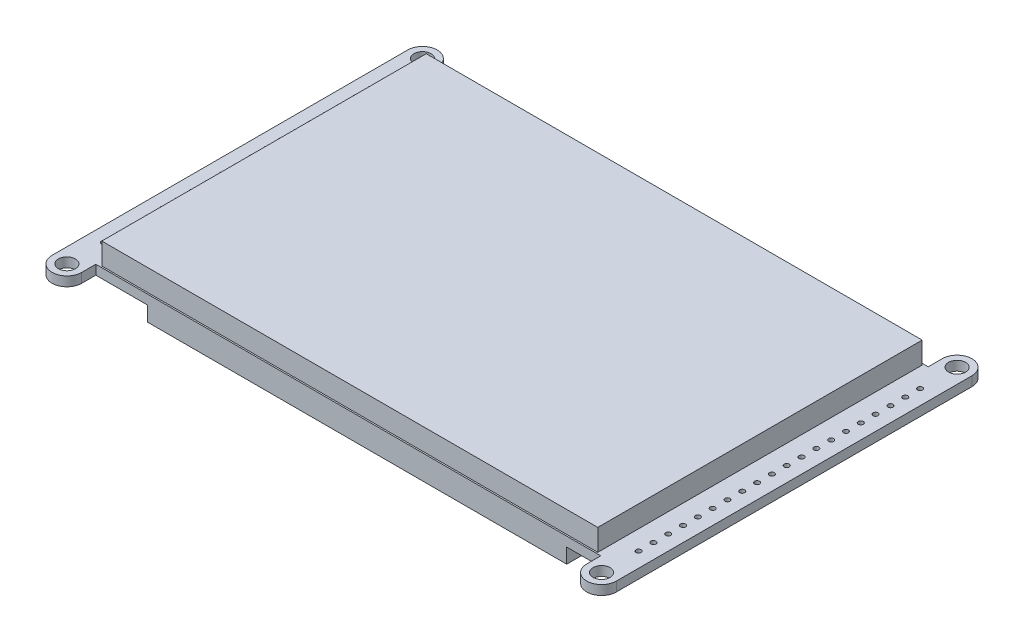
SolidWorks part; units mm, degrees
ref_plane "Front Plane" through (0, 0, 0) normal (0, 0, 1) x (1, 0, 0)
ref_plane "Top Plane" through (0, 0, 0) normal (0, 1, 0) x (1, 0, 0)
ref_plane "Right Plane" through (0, 0, 0) normal (1, 0, 0) x (0, 0, -1)
sketch "Sketch1" plane through (0, 0, 0) normal (0, 1, 0) x (1, 0, 0)
  line L0 (0, -28.067) -> (0, 28.067) construction
  line L1 (43.2943, 28.067) -> (-43.2943, 28.067)
  line L2 (43.2943, -28.067) -> (-43.2943, -28.067)
  line L3 (-43.2943, 28.067) -> (-43.2943, 30.48)
  line L4 (-48.3743, 30.48) -> (-48.3743, -30.48)
  line L5 (-43.2943, -30.48) -> (-43.2943, -28.067)
  line L6 (43.2943, -30.48) -> (43.2943, -28.067)
  line L7 (43.2943, 28.067) -> (43.2943, 30.48)
  line L8 (48.3743, 30.48) -> (48.3743, -30.48)
  line L9 (-45.8343, 24.13) -> (-45.8343, -24.13) construction
  line L10 (45.8343, 24.13) -> (45.8343, -24.13) construction
  line L12 (42.5196, -27.813) -> (-42.5196, -27.813)
  line L13 (42.5196, -27.813) -> (42.5196, 27.813)
  line L14 (42.5196, 27.813) -> (-42.5196, 27.813)
  line L15 (-42.5196, -27.813) -> (-42.5196, 27.813)
  line L16 (42.5196, -27.813) -> (-42.5196, 27.813) construction
  line L17 (42.5196, 27.813) -> (-42.5196, -27.813) construction
  circle A0 centre (-45.8343, 30.48) radius 1.4605
  arc A1 (-43.2943, 30.48) -> (-48.3743, 30.48) centre (-45.8343, 30.48) ccw
  arc A2 (-48.3743, -30.48) -> (-43.2943, -30.48) centre (-45.8343, -30.48) ccw
  circle A3 centre (-45.8343, -30.48) radius 1.4605
  circle A4 centre (45.8343, -30.48) radius 1.4605
  arc A5 (48.3743, -30.48) -> (43.2943, -30.48) centre (45.8343, -30.48) cw
  arc A6 (43.2943, 30.48) -> (48.3743, 30.48) centre (45.8343, 30.48) cw
  circle A7 centre (45.8343, 30.48) radius 1.4605
  circle A8 centre (-45.8343, 24.13) radius 0.4318
  circle A9 centre (-45.8343, 21.59) radius 0.4318
  circle A10 centre (-45.8343, 19.05) radius 0.4318
  circle A11 centre (-45.8343, 16.51) radius 0.4318
  circle A12 centre (-45.8343, 13.97) radius 0.4318
  circle A13 centre (-45.8343, 11.43) radius 0.4318
  circle A14 centre (-45.8343, 8.89) radius 0.4318
  circle A15 centre (-45.8343, 6.35) radius 0.4318
  circle A16 centre (-45.8343, 3.81) radius 0.4318
  circle A17 centre (-45.8343, 1.27) radius 0.4318
  circle A18 centre (-45.8343, -1.27) radius 0.4318
  circle A19 centre (-45.8343, -3.81) radius 0.4318
  circle A20 centre (-45.8343, -6.35) radius 0.4318
  circle A21 centre (-45.8343, -8.89) radius 0.4318
  circle A22 centre (-45.8343, -11.43) radius 0.4318
  circle A23 centre (-45.8343, -13.97) radius 0.4318
  circle A24 centre (-45.8343, -16.51) radius 0.4318
  circle A25 centre (-45.8343, -19.05) radius 0.4318
  circle A26 centre (-45.8343, -21.59) radius 0.4318
  circle A27 centre (-45.8343, -24.13) radius 0.4318
  circle A28 centre (45.8343, -24.13) radius 0.4318
  circle A29 centre (45.8343, -21.59) radius 0.4318
  circle A30 centre (45.8343, -19.05) radius 0.4318
  circle A31 centre (45.8343, -16.51) radius 0.4318
  circle A32 centre (45.8343, -13.97) radius 0.4318
  circle A33 centre (45.8343, -11.43) radius 0.4318
  circle A34 centre (45.8343, -8.89) radius 0.4318
  circle A35 centre (45.8343, -6.35) radius 0.4318
  circle A36 centre (45.8343, -3.81) radius 0.4318
  circle A37 centre (45.8343, -1.27) radius 0.4318
  circle A38 centre (45.8343, 1.27) radius 0.4318
  circle A39 centre (45.8343, 3.81) radius 0.4318
  circle A40 centre (45.8343, 6.35) radius 0.4318
  circle A41 centre (45.8343, 8.89) radius 0.4318
  circle A42 centre (45.8343, 11.43) radius 0.4318
  circle A43 centre (45.8343, 13.97) radius 0.4318
  circle A44 centre (45.8343, 16.51) radius 0.4318
  circle A45 centre (45.8343, 19.05) radius 0.4318
  circle A46 centre (45.8343, 21.59) radius 0.4318
  circle A47 centre (45.8343, 24.13) radius 0.4318
  point P3 (-45.8343, 0)
  point P4 (0, 0)
  point P8 (0, 28.067)
  point P11 (0, -28.067)
  point P19 (-45.8343, 33.02)
  point P22 (-45.8343, -33.02)
  point P23 (-48.3743, 0)
  point P35 (0, 0)
  dimension "D2" = 2.921
  dimension "D7" = 0.8636
  dimension "D1" = 66.04
  dimension "D3" = 5.08
  dimension "D4" = 56.134
  dimension "D5" = 96.7486
  dimension "D8" = 2.54
  dimension "D9" = 55.626
  dimension "D10" = 85.0392
  dimension "D6" = 20
extrude "Boss-Extrude1" add sketch "Sketch1" along normal blind 1.6256
extrude "Boss-Extrude2" add sketch "Sketch1<2>" along normal blind 5.334 contours L15 L12 L13 L14 region at (0, 0, 0)
sketch "Sketch1<2>" plane through (0, 0, 0) normal (0, 1, 0) x (1, 0, 0) same geometry as "Sketch1"
sketch "Sketch2" plane through (0, 0, 0) normal (0, -1, 0) x (1, 0, 0)
  line L0 (-48.3743, -30.48) -> (-48.3743, 30.48) construction
  line L1 (-34.4043, 28.067) -> (37.4523, 28.067)
  line L2 (-34.4043, 28.067) -> (-34.4043, -28.067)
  line L3 (-34.4043, -28.067) -> (37.4523, -28.067)
  line L4 (37.4523, 28.067) -> (37.4523, -28.067)
  line L5 (-34.4043, 28.067) -> (37.4523, -28.067) construction
  line L6 (-34.4043, -28.067) -> (37.4523, 28.067) construction
  line L7 (48.3743, 30.48) -> (48.3743, -30.48) construction
  line L8 (43.2943, -28.067) -> (-43.2943, -28.067) construction
  line L9 (-43.2943, 28.067) -> (43.2943, 28.067) construction
  point P0 (1.524, 0)
  dimension "D1" = 13.97
  dimension "D2" = 10.922
extrude "Boss-Extrude3" add sketch "Sketch2" along normal blind 2.54 contours L4 L1 L2 L3 region at (1.524, 0, 0)
